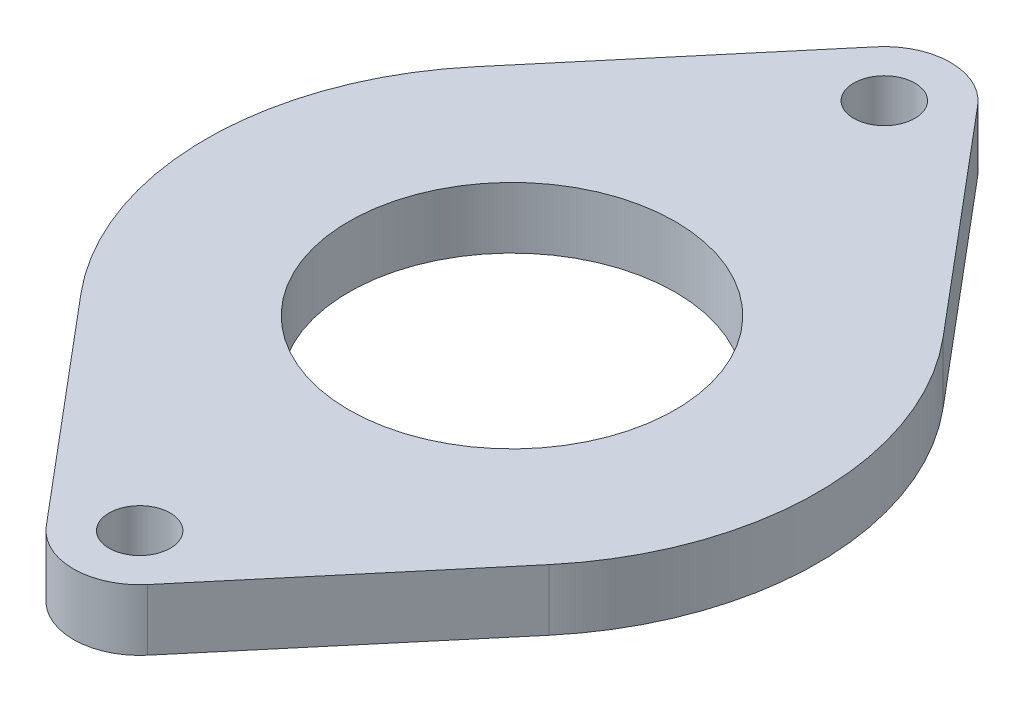
SolidWorks part; units mm, degrees
material "PEI"
ref_plane "Front Plane" through (0, 0, 0) normal (0, 0, 1) x (1, 0, 0)
ref_plane "Top Plane" through (0, 0, 0) normal (0, 1, 0) x (1, 0, 0)
ref_plane "Right Plane" through (0, 0, 0) normal (1, 0, 0) x (0, 0, -1)
sketch "Sketch1" plane through (0, 0, 0) normal (0, 1, 0) x (1, 0, 0)
  line L0 (0, -18.25) -> (0, 18.25)
  line L1 (2.4868, 20.3425) -> (11.4775, 9.6575)
  line L2 (-2.4868, 20.3425) -> (-11.4775, 9.6575)
  line L3 (0, 0) -> (15, 0)
  line L4 (-2.4868, -20.3425) -> (-11.4775, -9.6575)
  line L5 (2.4868, -20.3425) -> (11.4775, -9.6575)
  circle A0 centre (0, 0) radius 8
  circle A1 centre (0, 0) radius 15
  circle A2 centre (0, 18.25) radius 1.5
  circle A3 centre (0, 18.25) radius 3.25
  circle A4 centre (0, -18.25) radius 3.25
  circle A5 centre (0, -18.25) radius 1.5
  dimension "D1" = 16
  dimension "D2" = 30
  dimension "D4" = 3
  dimension "D3" = 18.25
extrude "Boss-Extrude1" add sketch "Sketch1" along normal blind 3 contours L3 A1 L0 A0 | L0 A1 A0 | L0 A1 L3 A0 | A1 A4 L5 | L4 A4 A1 | A5 A4 | A3 A1 L1 | A3 A2 | A3 L2 A1 region at (2.2331, 0, 16.0169) region at (-4.9857, 0, 15.4115) region at (-6.1884, 0, 13.2949) region at (7.5472, 0, 7.5472) region at (4.9857, 0, 15.4115) region at (7.5472, 0, -7.5472) region at (-4.9857, 0, -15.4115) region at (4.9857, 0, -15.4115) region at (-2.8631, 0, -16.9173)
